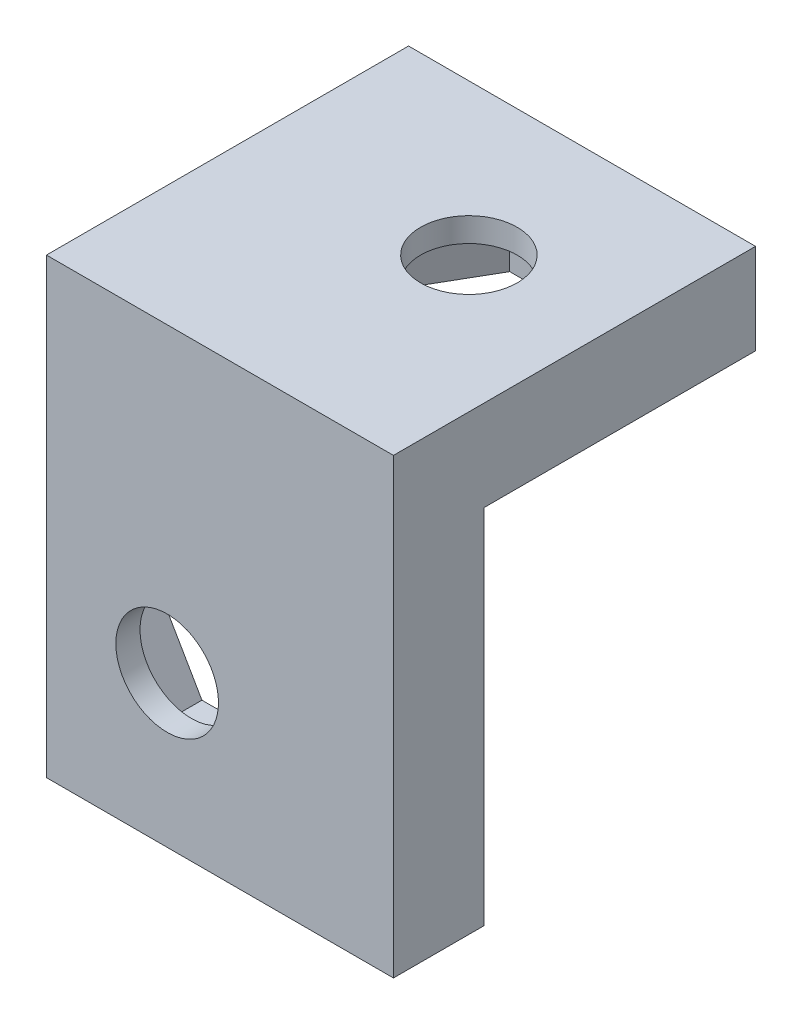
SolidWorks part; units mm, degrees
ref_plane "Front Plane" through (0, 0, 0) normal (0, 0, 1) x (1, 0, 0)
ref_plane "Top Plane" through (0, 0, 0) normal (0, 1, 0) x (1, 0, 0)
ref_plane "Right Plane" through (0, 0, 0) normal (1, 0, 0) x (0, 0, -1)
sketch "Sketch1" plane through (0, 0, 0) normal (0, 1, 0) x (1, 0, 0)
  line L0 (0, 7) -> (11.5, 7) construction
  line L1 (0, 0) -> (11.5, 0)
  line L2 (0, 0) -> (0, 12)
  line L3 (0, 12) -> (11.5, 12)
  line L4 (11.5, 0) -> (11.5, 12)
  line L6 (8.8475, 3.8) -> (10.695, 7)
  line L7 (10.695, 7) -> (8.8475, 10.2)
  line L8 (8.8475, 10.2) -> (5.1525, 10.2)
  line L9 (5.1525, 10.2) -> (3.305, 7)
  line L10 (3.305, 7) -> (5.1525, 3.8)
  line L11 (5.1525, 3.8) -> (8.8475, 3.8)
  line L12 (0, 0) -> (11.5, 0)
  line L13 (0, 0) -> (0, 3)
  line L14 (0, 3) -> (11.5, 3)
  line L15 (11.5, 0) -> (11.5, 3)
  circle A0 centre (7, 7) radius 3.2 construction
  circle A1 centre (7, 7) radius 1.6
  point P5 (7, 7)
  point P18 (10.3486, 7.5)
  dimension "D1" = 6.4
  dimension "D5" = 3.2
  dimension "D2" = 3
  dimension "D3" = 5
  dimension "D4" = 4
  dimension "D6" = 11.5
  dimension "D7" = 4.5
extrude "Boss-Extrude1" add sketch "Sketch1" along normal blind 3 contours L2 L14 L4 L3 L11 L10 L9 L8 L7 L6 | L10 L11 L6 L7 L8 L9 A1 | A1 | L14 L2 L1 L4 region at (5.75, 0, -1.5) region at (0.146, 0, -7.5) region at (7, 0, -3.8978) region at (7, 0, -7)
extrude "Boss-Extrude2" add sketch "Sketch1<4>" against normal blind 12 contours L14 L2 L1 L4 region at (5.75, 0, -1.5)
sketch "Sketch1<4>" plane through (0, 0, 0) normal (0, 1, 0) x (1, 0, 0) same geometry as "Sketch1"
extrude "Cut-Extrude1" cut sketch "Sketch1<5>" along normal blind 2.2 contours L10 L11 L6 L7 L8 L9 A1 region at (7, 0, -3.8978)
sketch "Sketch1<5>" plane through (0, 0, 0) normal (0, 1, 0) x (1, 0, 0) same geometry as "Sketch1"
extrude "Cut-Extrude2" cut sketch "Sketch1<6>" along normal through all contours A1
sketch "Sketch1<6>" plane through (0, 0, 0) normal (0, 1, 0) x (1, 0, 0) same geometry as "Sketch1"
sketch "Sketch3" plane through (0, 0, -3) normal (0, 0, -1) x (-1, 0, 0)
  line L0 (-11.5, -7) -> (0, -7)
  line L1 (-11.5, -12) -> (-11.5, 0) construction
  line L2 (0, -12) -> (0, 0) construction
  line L3 (0, 0) -> (-11.5, 0) construction
  line L4 (0, 0) -> (-11.5, 0) construction
  line L5 (-2.1525, -10.2) -> (-0.305, -7)
  line L6 (-0.305, -7) -> (-2.1525, -3.8)
  line L7 (-2.1525, -3.8) -> (-5.8475, -3.8)
  line L8 (-5.8475, -3.8) -> (-7.695, -7)
  line L9 (-7.695, -7) -> (-5.8475, -10.2)
  line L10 (-5.8475, -10.2) -> (-2.1525, -10.2)
  circle A0 centre (-4, -7) radius 1.7
  circle A1 centre (-4, -7) radius 3.2 construction
  point P8 (-4, -7)
  point P20 (-6.25, -5)
  point P21 (-6.25, -5)
  point P22 (-5.4059, -5.4979)
  dimension "D3" = 3.4
  dimension "D4" = 6.4
  dimension "D1" = 7
  dimension "D2" = 7.5
extrude "Cut-Extrude3" cut sketch "Sketch3" against normal blind 2.2 contours A0 L0 L9 L10 L5 | A0 L0 L6 L7 L8 region at (4, -5.2195, -3) region at (1.3025, -7.0805, -3)
extrude "Cut-Extrude4" cut sketch "Sketch3<3>" against normal through all contours L0 A0 | L0 A0 region at (4, -7.7215, -3) region at (4, -6.2785, -3)
sketch "Sketch3<3>" plane through (0, 0, -3) normal (0, 0, -1) x (-1, 0, 0) same geometry as "Sketch3"
